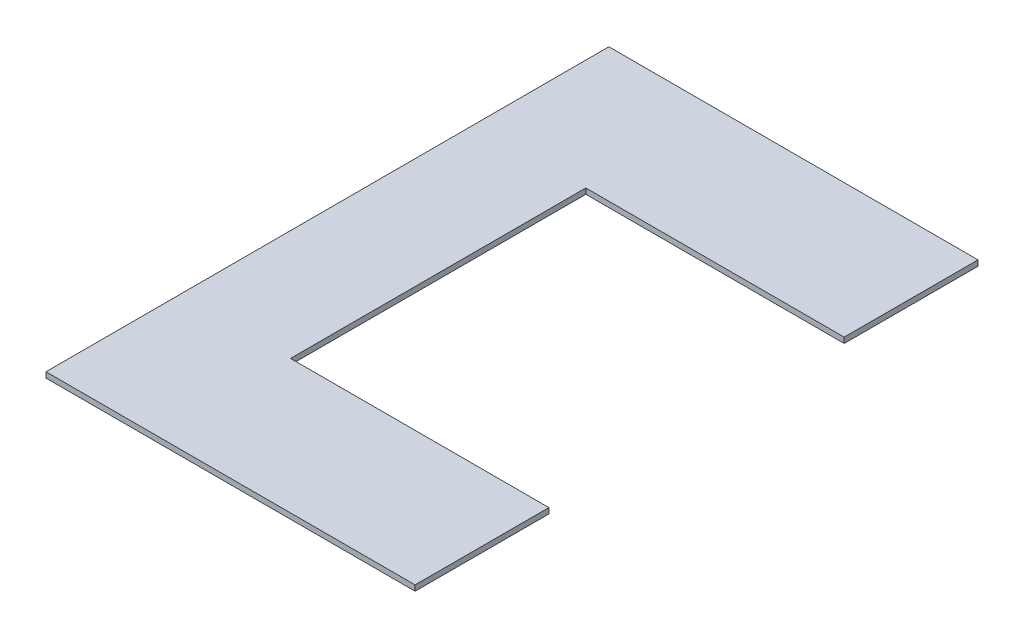
SolidWorks part; units mm, degrees
ref_plane "Alzado" through (0, 0, 0) normal (0, 0, 1) x (1, 0, 0)
ref_plane "Planta" through (0, 0, 0) normal (0, 1, 0) x (1, 0, 0)
ref_plane "Vista lateral" through (0, 0, 0) normal (1, 0, 0) x (0, 0, -1)
sketch "Croquis1" plane through (0, 0, 0) normal (0, 1, 0) x (1, 0, 0)
  line L0 (-100, 155) -> (0, 155)
  line L1 (-200, 155) -> (200, 155) construction
  line L2 (-200, 155) -> (-200, -155) construction
  line L3 (-200, -155) -> (200, -155) construction
  line L4 (200, 155) -> (200, -155) construction
  line L5 (-200, 155) -> (200, -155) construction
  line L6 (-200, -155) -> (200, 155) construction
  line L7 (-200, -155) -> (-150, -155)
  line L8 (-200, -155) -> (-200, 155)
  line L9 (-200, 155) -> (-150, 155)
  line L10 (0, -155) -> (0, 155)
  line L11 (-150, -151) -> (-100, -151) construction
  line L12 (-150, -151) -> (-150, -155) construction
  line L13 (-150, -155) -> (-100, -155) construction
  line L14 (-100, -151) -> (-100, -155) construction
  line L15 (-150, 151) -> (-100, 151) construction
  line L16 (-150, 151) -> (-150, 155) construction
  line L17 (-150, 155) -> (-100, 155) construction
  line L18 (-100, 151) -> (-100, 155) construction
  line L19 (-150, 151) -> (-100, 155) construction
  line L20 (-150, 155) -> (-100, 151) construction
  line L21 (-200, 105) -> (-196, 105) construction
  line L22 (-200, 105) -> (-200, 55) construction
  line L23 (-200, 55) -> (-196, 55) construction
  line L24 (-196, 105) -> (-196, 55) construction
  line L25 (-200, 105) -> (-196, 55) construction
  line L26 (-200, 55) -> (-196, 105) construction
  line L27 (-200, -55) -> (-196, -55) construction
  line L28 (-200, -55) -> (-200, -105) construction
  line L29 (-200, -105) -> (-196, -105) construction
  line L30 (-196, -55) -> (-196, -105) construction
  line L31 (-200, -55) -> (-196, -105) construction
  line L32 (-200, -105) -> (-196, -55) construction
  line L33 (-100, -155) -> (0, -155)
  line L34 (-200, 155) -> (-200, -155)
  line L35 (-150, 155) -> (-100, 155)
  line L36 (-150, -155) -> (-100, -155)
  point P0 (0, 0)
  point P16 (-125, 153)
  point P21 (-198, 80)
  point P26 (-198, -80)
  point P30 (-196, -105)
  dimension "D1" = 310
  dimension "D2" = 400
  dimension "D3" = 200
extrude "Saliente-Extruir1" add sketch "Croquis1" along normal blind 3 contours L9 L34 L7 L12 L11 L14 L33 L10 L0 L18 L15 L16 region at (-100, 0, 0)
sketch "Croquis2" plane through (0, 3, 0) normal (0, 1, 0) x (1, 0, 0)
  line L30 (0, -155) -> (0, 155) construction
  line L31 (-200, 155) -> (0, 155)
  line L32 (-200, 155) -> (-200, 152.5)
  line L33 (-200, 152.5) -> (0, 152.5)
  line L34 (0, 155) -> (0, 152.5)
  line L35 (-200, 155) -> (0, 152.5) construction
  line L36 (-200, 152.5) -> (0, 155) construction
  line L38 (-200, -155) -> (0, -155)
  line L39 (-200, -155) -> (-200, -152.5)
  line L40 (-200, -152.5) -> (0, -152.5)
  line L41 (0, -155) -> (0, -152.5)
  line L42 (-200, -155) -> (0, -152.5) construction
  line L43 (-200, -152.5) -> (0, -155) construction
  point P5 (-100, 153.75)
  point P12 (-100, -153.75)
  dimension "D1" = 2.5
extrude "Cortar-Extruir1" cut sketch "Croquis2" against normal blind 10
sketch "Croquis3" plane through (0, 3, 0) normal (0, 1, 0) x (1, 0, 0)
  line L0 (0, -152.5) -> (0, 152.5) construction
  line L1 (-140, 80) -> (0, 80)
  line L2 (-140, 80) -> (-140, -80)
  line L3 (-140, -80) -> (0, -80)
  line L4 (0, 80) -> (0, -80)
  line L5 (-140, 80) -> (0, -80) construction
  line L6 (-140, -80) -> (0, 80) construction
  line L8 (-200, -152.5) -> (-200, 152.5) construction
  point P0 (-70, 0)
  dimension "D1" = 160
  dimension "D2" = 60
extrude "Cortar-Extruir2" cut sketch "Croquis3" against normal blind 10
equation "\"D2@Croquis1\" = \"largo_tot\""
equation "\"D3@Croquis1\" = 200"
equation "\"D1@Croquis1\" = \"ancho_tot\""
equation "\"venesta\"= 4'grosor de la venesta"
equation "\"policarbonato\"= 4'grosor del policarbonato"
equation "\"carton_trupan\"= 3'grosor del carton trupan caso laser"
equation "\"ancho_tot\"= 310'ancho tot sin llantas"
equation "\"largo_tot\"= 400'largo tot sin camera"
equation "\"D1@Saliente-Extruir1\" = \"carton_trupan\""
equation "\"GROSOR_PARED_IMPRESION\"= 2.5mm"
equation "\"D1@Croquis2\"=\"GROSOR_PARED_IMPRESION\""
equation "\"apertura\"= 75"
